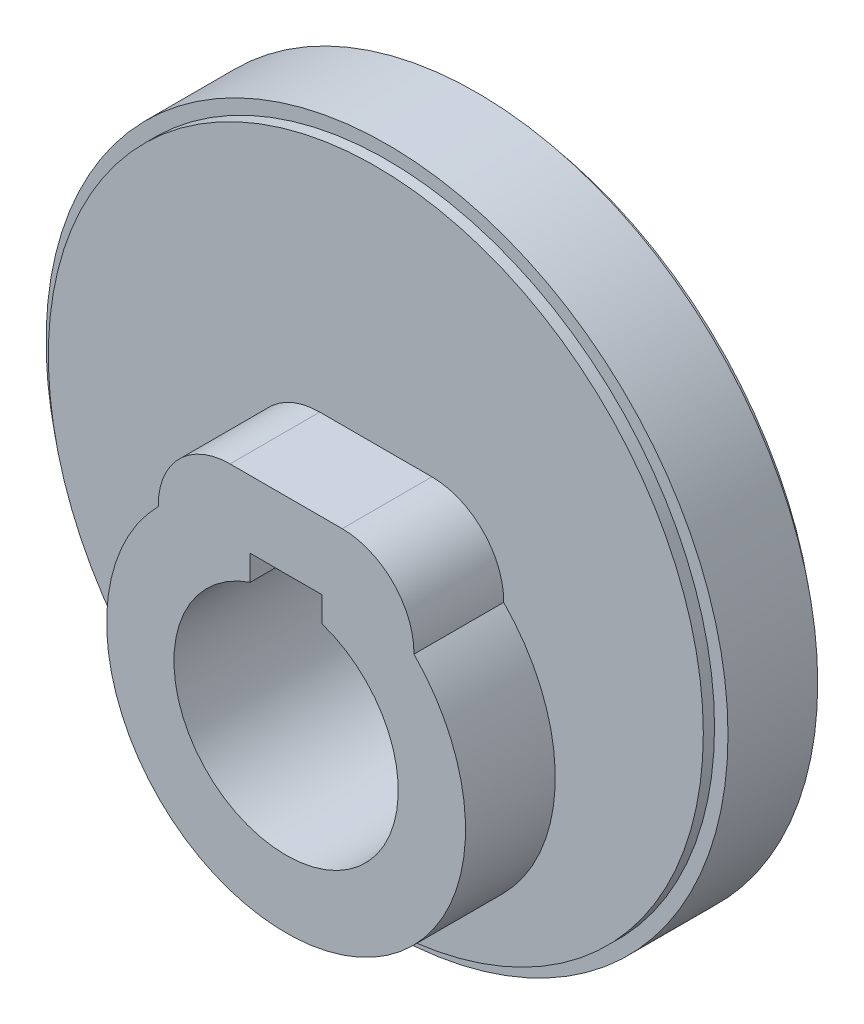
SolidWorks part; units mm, degrees
material "Copper"
ref_plane "Front Plane" through (0, 0, 0) normal (0, 0, 1) x (1, 0, 0)
ref_plane "Top Plane" through (0, 0, 0) normal (0, 1, 0) x (1, 0, 0)
ref_plane "Right Plane" through (0, 0, 0) normal (1, 0, 0) x (0, 0, -1)
sketch "Sketch1" plane through (0, 0, 0) normal (0, 0, 1) x (1, 0, 0)
  line L0 (1000, 0) -> (8, 0) construction
  line L1 (0, 0) -> (0, -48571.6145) construction
  line L2 (12.5, 49.6362) -> (12.5, 30.8905)
  line L3 (-12.5, 49.6362) -> (-12.5, 30.8905)
  line L4 (-8, 4.3) -> (8, 4.3)
  line L5 (8, 4.3) -> (8, -1.3146)
  line L6 (-8, 4.3) -> (-8, -1.3146)
  line L7 (-8, 0) -> (-48571.6145, 0) construction
  line L8 (-12.5, 19.3) -> (12.5, 19.3)
  circle A0 centre (0, 0) radius 76
  circle A1 centre (0, 0) radius 73
  arc A2 (-8, -1.3146) -> (8, -1.3146) centre (0, -25) ccw
  arc A3 (-28.4983, 3.0686) -> (28.4983, 3.0686) centre (0, -25) ccw
  arc A4 (49.3059, -0.6293) -> (14.6983, 27.9996) centre (0, -25) ccw
  arc A5 (54.995, 0.7404) -> (16.3942, 52.4998) centre (0, 0) ccw
  arc A6 (-14.6983, 27.9996) -> (-49.3059, -0.6293) centre (0, -25) ccw
  arc A7 (-16.3942, 52.4998) -> (-54.995, 0.7404) centre (0, 0) ccw
  arc A8 (14.6983, 27.9996) -> (12.5, 30.8905) centre (15.5, 30.8905) cw
  arc A9 (12.5, 49.6362) -> (16.3942, 52.4998) centre (15.5, 49.6362) cw
  arc A10 (-54.995, 0.7404) -> (-49.3059, -0.6293) centre (-51.9953, 0.7) ccw
  arc A11 (-12.5, 30.8905) -> (-14.6983, 27.9996) centre (-15.5, 30.8905) cw
  arc A12 (-12.5, 49.6362) -> (-16.3942, 52.4998) centre (-15.5, 49.6362) ccw
  arc A13 (49.3059, -0.6293) -> (54.995, 0.7404) centre (51.9953, 0.7) ccw
  arc A14 (28.4983, 3.0686) -> (12.5, 19.3) centre (12.5, 3.3) ccw
  arc A15 (-28.4983, 3.0686) -> (-12.5, 19.3) centre (-12.5, 3.3) cw
  point P20 (0, 4.3)
  point P28 (-12.5, 28.5607)
  point P31 (-12.5, 53.5607)
  point P40 (0, -20.7)
  point P41 (0, 19.3)
  dimension "D1" = 152
  dimension "D2" = 146
  dimension "D3" = 50
  dimension "D5" = 80
  dimension "D6" = 110
  dimension "D7" = 110
  dimension "D10" = 3
  dimension "D11" = 3
  dimension "D14" = 32
  dimension "D4" = 25
  dimension "D8" = 25
  dimension "D9" = 16
  dimension "D12" = 29.3
  dimension "D13" = 15
  dimension "D15" = 16
  dimension "D16" = 25
extrude "Boss-Extrude1" add sketch "Sketch1" along normal blind 25 contours A1 A12 L3 A11 A6 A10 A7 A13 A4 A8 L2 A9 A5 A3 A15 L8 A14 | L3 A12 A7 A10 A6 A11 | A4 A13 A5 A9 L2 A8 region at (33.0865, 28.6094, 0) region at (-33.0865, 28.6094, 0) region at (-70.9352, 0, 0)
extrude "Boss-Extrude2" add sketch "Sketch1<3>" along normal blind 20 from offset 2.5 contours A0 A1 region at (-73.8504, 0, 0)
sketch "Sketch1<3>" plane through (0, 0, 0) normal (0, 0, 1) x (1, 0, 0) same geometry as "Sketch1"
extrude "Boss-Extrude3" add sketch "Sketch1<4>" along normal blind 45 contours A15 A3 A14 L8 A2 L6 L4 L5 region at (0, 18.1378, 0)
sketch "Sketch1<4>" plane through (0, 0, 0) normal (0, 0, 1) x (1, 0, 0) same geometry as "Sketch1"
extrude "Cut-Extrude1" cut sketch "Sketch1<5>" along normal blind 10 contours A4 A13 A5 A9 L2 A8 | L3 A12 A7 A10 A6 A11 region at (33.0865, 28.6094, 0) region at (-33.0865, 28.6094, 0)
sketch "Sketch1<5>" plane through (0, 0, 0) normal (0, 0, 1) x (1, 0, 0) same geometry as "Sketch1"
